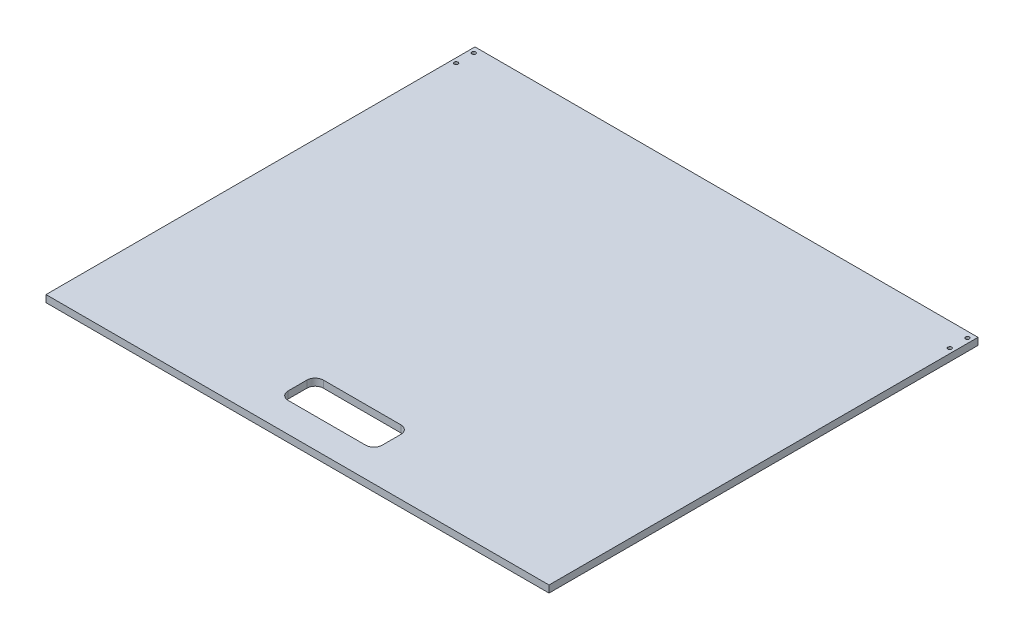
SolidWorks part; units mm, degrees
ref_plane "Front Plane" through (0, 0, 0) normal (0, 0, 1) x (1, 0, 0)
ref_plane "Top Plane" through (0, 0, 0) normal (0, 1, 0) x (1, 0, 0)
ref_plane "Right Plane" through (0, 0, 0) normal (1, 0, 0) x (0, 0, -1)
sketch "Sketch1" plane through (0, 0, 0) normal (0, 1, 0) x (1, 0, 0)
  line L1 (-214, -182.5) -> (214, -182.5)
  line L2 (-214, -182.5) -> (-214, 182.5)
  line L3 (-214, 182.5) -> (214, 182.5)
  line L4 (214, -182.5) -> (214, 182.5)
  line L5 (-214, -182.5) -> (214, 182.5) construction
  line L6 (-214, 182.5) -> (214, -182.5) construction
  point P0 (0, 0)
  dimension "D1" = 428
  dimension "D2" = 365
extrude "Boss-Extrude1" add sketch "Sketch1" along normal blind 6
sketch "Sketch2" plane through (0, 0, 0) normal (0, -1, 0) x (1, 0, 0)
  line L0 (214, -182.5) -> (-214, -182.5) construction
  line L1 (214, 182.5) -> (214, -182.5) construction
  circle A0 centre (210, -162.5) radius 1.6
  circle A1 centre (210, -177.5) radius 1.6
  dimension "D1" = 5
  dimension "D3" = 3.2
  dimension "D2" = 15
  dimension "D4" = 4
extrude "Cut-Extrude1" cut sketch "Sketch2" against normal through all
mirror "Mirror1" about plane through (0, 0, 0) normal (1, 0, 0) of "Cut-Extrude1"
sketch "Sketch3" plane through (0, 6, 0) normal (0, 1, 0) x (1, 0, 0)
  line L0 (-214, -182.5) -> (214, -182.5) construction
  line L1 (-33, -157.5) -> (33, -157.5)
  line L2 (-40, -150.5) -> (-40, -134.5)
  line L3 (-33, -127.5) -> (33, -127.5)
  line L4 (40, -150.5) -> (40, -134.5)
  line L5 (-40, -157.5) -> (40, -127.5) construction
  line L6 (-40, -127.5) -> (40, -157.5) construction
  arc A0 (-40, -134.5) -> (-33, -127.5) centre (-33, -134.5) cw
  arc A1 (-33, -157.5) -> (-40, -150.5) centre (-33, -150.5) cw
  arc A2 (33, -157.5) -> (40, -150.5) centre (33, -150.5) ccw
  arc A3 (33, -127.5) -> (40, -134.5) centre (33, -134.5) cw
  point P0 (0, -142.5)
  dimension "D4" = 7
  dimension "D1" = 25
  dimension "D2" = 80
  dimension "D3" = 30
extrude "Cut-Extrude2" cut sketch "Sketch3" against normal through all
